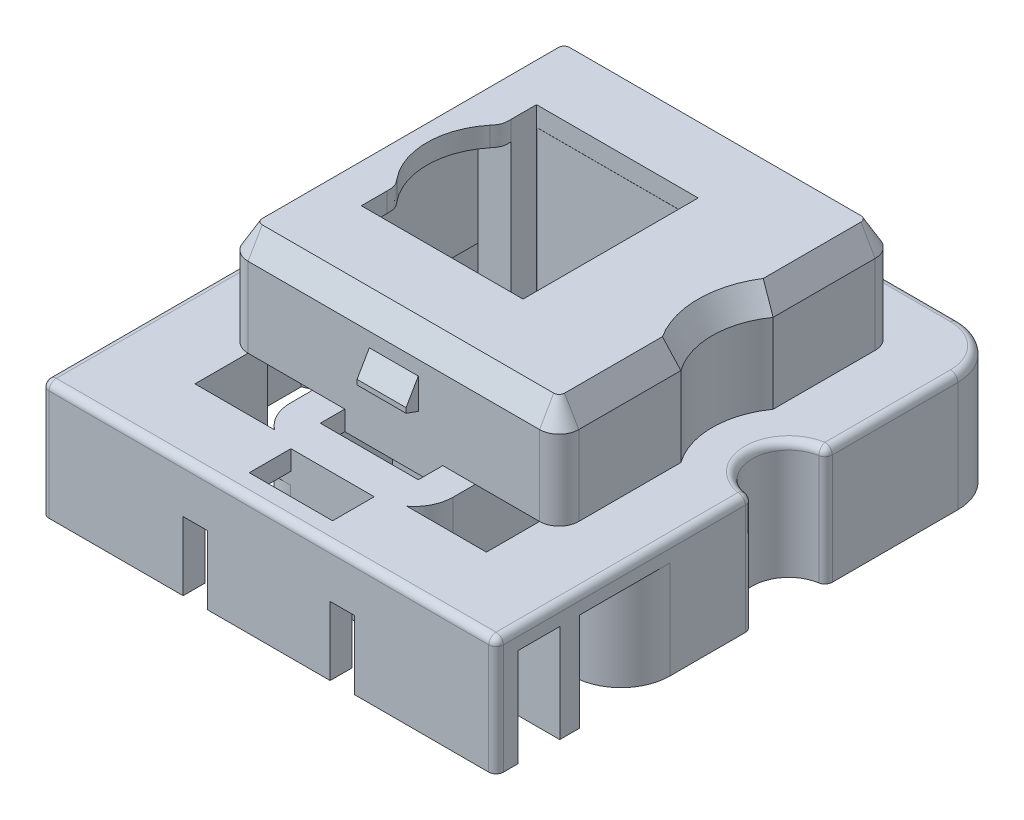
SolidWorks part; units mm, degrees
ref_plane "Front Plane" through (0, 0, 0) normal (0, 0, 1) x (1, 0, 0)
ref_plane "Top Plane" through (0, 0, 0) normal (0, 1, 0) x (1, 0, 0)
ref_plane "Right Plane" through (0, 0, 0) normal (1, 0, 0) x (0, 0, -1)
ref_plane "Floor" through (0, -4, 0) normal (0, -1, 0) x (-1, 0, 0)
sketch "Sketch1" plane through (0, 0, 0) normal (0, 1, 0) x (1, 0, 0)
  line L0 (9.275, -1.5) -> (9.275, -11.95)
  line L1 (-9.275, 8.9) -> (9.275, 8.9)
  line L2 (-9.275, 8.9) -> (-9.275, 1.5)
  line L3 (-9.275, -11.95) -> (9.275, -11.95)
  line L4 (9.275, 8.9) -> (9.275, 1.5)
  line L5 (-9.275, 8.9) -> (9.275, -11.95) construction
  line L6 (-9.275, -11.95) -> (9.275, 8.9) construction
  line L7 (-9.275, -1.5) -> (-9.275, -11.95)
  arc A0 (9.275, 1.5) -> (9.275, -1.5) centre (9.275, 0) ccw
  arc A1 (-9.275, -1.5) -> (-9.275, 1.5) centre (-9.275, 0) ccw
  point P0 (0, -1.525)
  dimension "D4" = 3
  dimension "D5" = 3
  dimension "D1" = 18.55
  dimension "D2" = 20.85
  dimension "D3" = 8.9
extrude "Boss-Extrude1" add sketch "Sketch1" along normal blind 0.8
sketch "Sketch2" plane through (0, 0.8, 0) normal (0, 1, 0) x (1, 0, 0)
  line L0 (6.75, -1.8815) -> (6.75, -6.85)
  line L1 (-6.75, 6.85) -> (6.75, 6.85)
  line L2 (-6.75, 6.85) -> (-6.75, -6.85)
  line L3 (-6.75, -6.85) -> (6.75, -6.85)
  line L4 (6.75, 6.85) -> (6.75, 1.8815)
  line L5 (-6.75, 6.85) -> (6.75, -6.85) construction
  line L6 (-6.75, -6.85) -> (6.75, 6.85) construction
  arc A0 (6.75, 1.8815) -> (6.75, -1.8815) centre (9.4, 0) ccw
  point P0 (0, 0)
  dimension "D3" = 6.5
  dimension "D1" = 13.5
  dimension "D2" = 13.7
  dimension "D4" = 9.4
extrude "Boss-Extrude2" add sketch "Sketch2" along normal blind 4.25
sketch "Sketch15" plane through (0, 0, 0) normal (0, -1, 0) x (1, 0, 0)
  line L0 (5.95, -2.1213) -> (5.95, -6.05)
  line L1 (5.95, 6.05) -> (-5.95, 6.05)
  line L2 (5.95, 6.05) -> (5.95, 2.1213)
  line L3 (5.95, -6.05) -> (-5.95, -6.05)
  line L4 (-5.95, 6.05) -> (-5.95, -6.05)
  line L5 (5.95, 6.05) -> (-5.95, -6.05) construction
  line L6 (5.95, -6.05) -> (-5.95, 6.05) construction
  arc A0 (5.95, 2.1213) -> (5.95, -2.1213) centre (9.4, 0) ccw
  point P0 (0, 0)
  dimension "D3" = 8.1
  dimension "D1" = 11.9
  dimension "D2" = 12.1
  dimension "D4" = 9.4
extrude "Cut-Extrude3" cut sketch "Sketch15" against normal blind 4.25
ref_plane "Plane2" through (0, 2.3, 0) normal (0, 1, 0) x (1, 0, 0)
sketch "Sketch6" plane through (0, 0, 6.85) normal (0, 0, 1) x (1, 0, 0)
  line L0 (-6.75, 0.8) -> (6.75, 0.8) construction
  line L1 (-1, 2.6) -> (1, 2.6)
  line L2 (-1, 2.6) -> (-1, 2.4)
  line L3 (-1, 2.4) -> (1, 2.4)
  line L4 (1, 2.6) -> (1, 2.4)
  line L5 (-1, 2.6) -> (1, 2.4) construction
  line L6 (-1, 2.4) -> (1, 2.6) construction
  point P0 (0, 2.5)
  dimension "D1" = 1.6
  dimension "D2" = 0.2
  dimension "D3" = 2
extrude "Boss-Extrude4" add sketch "Sketch6" along normal blind 0.5
draft "Draft1" type of draft neutral plane draft angle 60 faces to draft 1 face at (0, 2.6, 7.1) neutral plane through (0, 0, 7.35) neutral plane normal (0, 0, 1) parameters "D1"=60
draft "Draft4" type of draft neutral plane draft angle 20 faces to draft 1 face at (0, 2.4, 7.1) neutral plane through (0, 0, 7.35) neutral plane normal (0, 0, 1) parameters "D1"=20
sketch "Sketch7" plane through (0, 0.8, 0) normal (0, 1, 0) x (1, 0, 0)
  line L0 (-6.75, -6.85) -> (6.75, -6.85) construction
  line L1 (-2, -6.85) -> (2, -6.85)
  line L2 (-2, -6.85) -> (-2, -7.85)
  line L3 (-2, -7.85) -> (2, -7.85)
  line L4 (2, -6.85) -> (2, -7.85)
  line L5 (-2, -6.85) -> (2, -7.85) construction
  line L6 (-2, -7.85) -> (2, -6.85) construction
  point P0 (0, -7.35)
  dimension "D1" = 1
  dimension "D2" = 4
extrude "Cut-Extrude1" cut sketch "Sketch7" against normal through all
mirror "Mirror1" about plane through (0, 0, 0) normal (0, 0, 1) of "Draft4", "Draft1", "Boss-Extrude4", "Cut-Extrude1"
sketch "Sketch8" plane through (0, 0, 0) normal (0, 1, 0) x (1, 0, 0)
  line L1 (9.275, -11.05) -> (-9.275, -11.05)
  line L2 (9.275, -11.05) -> (9.275, -11.95)
  line L3 (9.275, -11.95) -> (-9.275, -11.95)
  line L4 (-9.275, -11.05) -> (-9.275, -11.95)
  line L5 (9.275, -11.05) -> (-9.275, -11.95) construction
  line L6 (9.275, -11.95) -> (-9.275, -11.05) construction
  line L8 (-9.275, -11.95) -> (9.275, -11.95) construction
  point P0 (0, -11.5)
  dimension "D1" = 0.9
extrude "Boss-Extrude5" add sketch "Sketch8" against normal up to surface (4 mm away) up to plane "Floor"
sketch "Sketch9" plane through (0, -4, 0) normal (0, -1, 0) x (-1, 0, 0)
  line L0 (9.275, -11.95) -> (-9.275, -11.95) construction
  line L1 (-9.275, -11.05) -> (9.275, -11.05) construction
  line L7 (-2.5, -11.95) -> (-3.5, -11.95)
  line L8 (-2.5, -11.95) -> (-2.5, -11.05)
  line L9 (-2.5, -11.05) -> (-3.5, -11.05)
  line L10 (-3.5, -11.95) -> (-3.5, -11.05)
  line L11 (-2.5, -11.95) -> (-3.5, -11.05) construction
  line L12 (-2.5, -11.05) -> (-3.5, -11.95) construction
  point P5 (-3, -11.5)
  dimension "D1" = 1
  dimension "D2" = 2.5
extrude "Cut-Extrude2" cut sketch "Sketch9" against normal blind 2.8
mirror "Mirror2" about plane through (0, 0, 0) normal (1, 0, 0) of "Cut-Extrude2"
sketch "Sketch11" plane through (0, 0, 0) normal (0, -1, 0) x (1, 0, 0)
  line L0 (9.275, 11.05) -> (9.275, 1.5) construction
  line L1 (5.95, 9.35) -> (9.275, 9.35)
  line L2 (5.95, 9.35) -> (5.95, 6.05)
  line L3 (9.275, 8.55) -> (6.75, 8.55)
  line L4 (9.275, 9.35) -> (9.275, 8.55)
  line L5 (9.275, 11.05) -> (-9.275, 11.05) construction
  line L6 (6.75, 8.55) -> (6.75, 6.85)
  line L7 (6.75, 6.85) -> (7.275, 6.85)
  line L8 (9.275, 4.85) -> (9.275, 1.5)
  line L9 (5.95, 6.05) -> (7.275, 6.05)
  line L10 (8.475, 4.85) -> (8.475, 2.1564)
  line L11 (9.275, -1.5) -> (9.275, -8.9)
  line L12 (9.275, -1.5) -> (9.275, -8.9) construction
  line L13 (8.475, -8.9) -> (8.475, -2.1564)
  line L14 (9.275, -8.9) -> (-9.275, -8.9) construction
  line L15 (8.475, -8.9) -> (9.275, -8.9)
  line L16 (5.95, 2.1213) -> (5.95, 6.05) construction
  line L17 (5.95, 6.05) -> (-5.95, 6.05) construction
  arc A0 (9.275, 1.5) -> (9.275, -1.5) centre (9.275, 0) ccw
  arc A1 (8.475, 2.1564) -> (8.475, -2.1564) centre (9.275, 0) ccw
  arc A2 (7.275, 6.05) -> (8.475, 4.85) centre (7.275, 4.85) cw
  arc A3 (7.275, 6.85) -> (9.275, 4.85) centre (7.275, 4.85) cw
  point P24 (9.275, 6.85)
  dimension "D4" = 3
  dimension "D5" = 4.6
  dimension "D10" = 1.2
  dimension "D11" = 2
  dimension "D1" = 1.7
  dimension "D2" = 0.8
  dimension "D6" = 0.8
  dimension "D7" = 0.8
  dimension "D8" = 0.8
  dimension "D12" = 0.8
extrude "Boss-Extrude6" add sketch "Sketch11" along normal up to surface (4 mm away) up to plane "Floor"
sketch "Sketch12" plane through (0, 0, 0) normal (0, -1, 0) x (1, 0, 0)
  line L1 (5.95, 11.05) -> (6.75, 11.05)
  line L2 (5.95, 11.05) -> (5.95, 9.35)
  line L3 (5.95, 9.35) -> (6.75, 9.35)
  line L4 (6.75, 11.05) -> (6.75, 9.35)
  line L5 (9.275, 11.05) -> (-9.275, 11.05) construction
  line L6 (9.275, 9.35) -> (5.95, 9.35) construction
  line L7 (5.95, 9.35) -> (5.95, 6.05) construction
  line L8 (6.75, 6.85) -> (6.75, 8.55) construction
extrude "Boss-Extrude7" add sketch "Sketch12" along normal blind 1.5
mirror "Mirror3" about plane through (0, 0, 0) normal (1, 0, 0) of "Boss-Extrude7", "Boss-Extrude6"
sketch "Sketch19" plane through (0, 0, 0) normal (0, -1, 0) x (1, 0, 0)
  line L0 (8.475, -8.9) -> (-8.475, -8.9) construction
  line L1 (-4.55, -3.57) -> (4.55, -3.57)
  line L2 (-4.55, -3.57) -> (-4.55, -8.9)
  line L3 (-4.55, -8.9) -> (4.55, -8.9)
  line L4 (4.55, -3.57) -> (4.55, -8.9)
  line L5 (-4.55, -3.57) -> (4.55, -8.9) construction
  line L6 (-4.55, -8.9) -> (4.55, -3.57) construction
  line L8 (-3.75, -8.1) -> (3.75, -8.1)
  line L9 (-3.75, -8.1) -> (-3.75, -4.37)
  line L10 (-3.75, -4.37) -> (3.75, -4.37)
  line L11 (3.75, -8.1) -> (3.75, -4.37)
  line L12 (-3.75, -8.1) -> (3.75, -4.37) construction
  line L13 (-3.75, -4.37) -> (3.75, -8.1) construction
  point P0 (0, -6.235)
  point P7 (0, -8.9)
  point P9 (0, -6.235)
  dimension "D1" = 5.33
  dimension "D2" = 9.1
  dimension "D3" = 0.8
  dimension "D4" = 0.8
sketch "Sketch13" plane through (0, 0, 0) normal (0, -1, 0) x (1, 0, 0)
  line L0 (8.475, -8.9) -> (-8.475, -8.9) construction
  line L1 (8.475, -8.1) -> (-8.475, -8.1)
  line L2 (8.475, -8.1) -> (8.475, -8.9)
  line L3 (8.475, -8.9) -> (-8.475, -8.9)
  line L4 (-8.475, -8.1) -> (-8.475, -8.9)
  line L5 (8.475, -8.1) -> (-8.475, -8.9) construction
  line L6 (8.475, -8.9) -> (-8.475, -8.1) construction
  point P0 (0, -8.5)
  point P7 (0, -8.9)
  dimension "D1" = 0.8
extrude "Boss-Extrude8" add sketch "Sketch13" along normal up to surface (4 mm away) up to plane "Floor"
fillet "Fillet1" radius 1.2 2 edges at (8.475, -2, -8.1) (-8.475, -2, -8.1)
fillet "Fillet2" radius 2 2 edges at (9.275, -1.6, -8.9) (-9.275, -1.6, -8.9)
fillet "Fillet3" radius 0.3 16 edges at (9.275, 0.8, -4.2) (8.6892, 0.8, -8.3142) (0, 0.8, -8.9) (-8.6892, 0.8, -8.3142) (7.775, 0.8, 0) (-7.775, 0.8, 0) (-9.275, 0.8, 6.725) (0, 0.8, 11.95) (9.275, 0.8, 6.725) (-9.275, 0.8, -4.2) (-9.275, -1.6, -1.5) (-9.275, -1.6, 1.5) (9.275, -1.6, -1.5) (9.275, -1.6, 1.5) (-9.275, -1.6, 11.95) (9.275, -1.6, 11.95)
fillet "Fillet5" radius 0.8 4 edges at (-6.75, 2.925, -6.85) (6.75, 2.925, -6.85) (-6.75, 2.925, 6.85) (6.75, 2.925, 6.85)
chamfer "Chamfer1" distance 1 angle 30 10 edges at (6.5157, 5.05, -6.6157) (0, 5.05, -6.85) (-6.5157, 5.05, -6.6157) (-6.75, 5.05, 0) (-6.5157, 5.05, 6.6157) (6.75, 5.05, -3.9657) (0, 5.05, 6.85) (6.75, 5.05, 3.9657) (6.5157, 5.05, 6.6157) (6.15, 5.05, 0) first distance on face at (6.4328, 2.925, -6.5328) first distance on face at (0, 2.842, -6.85) first distance on face at (-6.4328, 2.925, -6.5328) first distance on face at (-6.75, 2.925, 0) first distance on face at (-6.4328, 2.925, 6.5328) first distance on face at (6.75, 2.925, -3.9657) first distance on face at (0, 1.6625, 6.85) first distance on face at (6.75, 2.925, 3.9657) first distance on face at (6.4328, 2.925, 6.5328) first distance on face at (6.45, 2.925, 0)
sketch "Sketch14" plane through (0, 0, 0) normal (0, -1, 0) x (1, 0, 0)
  line L0 (9.275, 9.35) -> (6.75, 9.35) construction
  line L1 (-1.725, 9.35) -> (1.725, 9.35)
  line L2 (-3.325, 7.75) -> (-3.325, 3.57)
  line L3 (-3.325, 3.57) -> (3.325, 3.57)
  line L4 (3.325, 7.75) -> (3.325, 3.57)
  line L5 (-3.325, 9.35) -> (3.325, 3.57) construction
  line L6 (-3.325, 3.57) -> (3.325, 9.35) construction
  line L8 (-1.725, 8.55) -> (1.725, 8.55)
  line L9 (-2.525, 7.75) -> (-2.525, 4.37)
  line L10 (-2.525, 4.37) -> (2.525, 4.37)
  line L11 (2.525, 7.75) -> (2.525, 4.37)
  line L12 (-2.525, 8.55) -> (2.525, 4.37) construction
  line L13 (-2.525, 4.37) -> (2.525, 8.55) construction
  arc A0 (-1.725, 9.35) -> (-3.325, 7.75) centre (-1.725, 7.75) ccw
  arc A1 (1.725, 9.35) -> (3.325, 7.75) centre (1.725, 7.75) cw
  arc A2 (-1.725, 8.55) -> (-2.525, 7.75) centre (-1.725, 7.75) ccw
  arc A3 (1.725, 8.55) -> (2.525, 7.75) centre (1.725, 7.75) cw
  point P0 (0, 6.46)
  point P10 (0, 6.46)
  dimension "D5" = 1.6
  dimension "D6" = 0.8
  dimension "D1" = 6.65
  dimension "D2" = 5.78
  dimension "D3" = 0.8
  dimension "D4" = 0.8
extrude "Boss-Extrude9" add sketch "Sketch14" along normal up to surface (4 mm away) up to plane "Floor"
sketch "Sketch16" plane through (0, 0, 0) normal (0, -1, 0) x (1, 0, 0)
  line L8 (-3.325, 6.05) -> (-3.325, 3.57)
  line L9 (-2.525, 6.05) -> (-3.325, 6.05)
  line L10 (-2.525, 4.37) -> (-2.525, 6.05)
  line L11 (2.525, 4.37) -> (-2.525, 4.37)
  line L12 (2.525, 6.05) -> (2.525, 4.37)
  line L13 (3.325, 6.05) -> (2.525, 6.05)
  line L14 (3.325, 3.57) -> (3.325, 6.05)
  line L15 (-3.325, 3.57) -> (3.325, 3.57)
  line L16 (-3.325, 6.05) -> (-3.325, 3.57)
  line L17 (-2.525, 6.05) -> (-3.325, 6.05)
  line L18 (-2.525, 4.37) -> (-2.525, 6.05)
  line L19 (2.525, 4.37) -> (-2.525, 4.37)
  line L20 (2.525, 6.05) -> (2.525, 4.37)
  line L21 (3.325, 6.05) -> (2.525, 6.05)
  line L22 (3.325, 3.57) -> (3.325, 6.05)
  line L23 (-3.325, 3.57) -> (3.325, 3.57)
  dimension "D1" = 0
extrude "Boss-Extrude10" add sketch "Sketch16" against normal up to surface (4.25 mm away) up to face at (1.8833, 4.25, 0)
sketch "Sketch17" plane through (0, 0, 0) normal (0, -1, 0) x (1, 0, 0)
  line L0 (5.95, 11.05) -> (-5.95, 11.05) construction
  line L1 (-1.7, 11.05) -> (1.7, 11.05)
  line L2 (-1.7, 11.05) -> (-1.7, 9.35)
  line L3 (-1.7, 9.35) -> (1.7, 9.35)
  line L4 (1.7, 11.05) -> (1.7, 9.35)
  line L5 (-1.7, 11.05) -> (1.7, 9.35) construction
  line L6 (-1.7, 9.35) -> (1.7, 11.05) construction
  line L7 (1.725, 9.35) -> (-1.725, 9.35) construction
  point P0 (0, 10.2)
  dimension "D1" = 3.4
extrude "Cut-Extrude4" cut sketch "Sketch17" against normal through all
sketch "Sketch18" plane through (0, 0, 11.05) normal (0, 0, -1) x (-1, 0, 0)
  line L1 (1.4, -3.1) -> (-1.4, -3.1)
  line L2 (1.4, -3.1) -> (1.4, -3.3)
  line L3 (1.4, -3.3) -> (-1.4, -3.3)
  line L4 (-1.4, -3.1) -> (-1.4, -3.3)
  line L5 (1.4, -3.1) -> (-1.4, -3.3) construction
  line L6 (1.4, -3.3) -> (-1.4, -3.1) construction
  line L7 (-6.75, -1.5) -> (-5.95, -1.5) construction
  point P0 (0, -3.2)
  dimension "D1" = 1.6
  dimension "D2" = 0.2
  dimension "D3" = 2.8
extrude "Boss-Extrude11" add sketch "Sketch18" along normal blind 0.25
draft "Draft2" type of draft neutral plane draft angle 60 faces to draft 1 face at (0, -3.3, 10.925) neutral plane through (0, 0, 10.8) neutral plane normal (0, 0, -1) parameters "D1"=60
draft "Draft3" type of draft neutral plane draft angle 20 faces to draft 1 face at (0, -3.1, 10.925) neutral plane through (0, 0, 10.8) neutral plane normal (0, 0, -1) parameters "D1"=20
ref_plane "Plane4" through (0, 0, 10.2) normal (0, 0, -1) x (-1, 0, 0)
mirror "Mirror4" about plane through (0, 0, 10.2) normal (0, 0, -1) of "Draft3", "Draft2", "Boss-Extrude11"
extrude "Boss-Extrude12" add sketch "Sketch19" along normal up to surface (4 mm away) up to plane "Floor"
sketch "Sketch20" plane through (0, 0, 0) normal (0, -1, 0) x (1, 0, 0)
  line L8 (4.55, -6.05) -> (4.55, -3.57)
  line L9 (3.75, -6.05) -> (4.55, -6.05)
  line L10 (3.75, -4.37) -> (3.75, -6.05)
  line L11 (-3.75, -4.37) -> (3.75, -4.37)
  line L12 (-3.75, -6.05) -> (-3.75, -4.37)
  line L13 (-4.55, -6.05) -> (-3.75, -6.05)
  line L14 (-4.55, -3.57) -> (-4.55, -6.05)
  line L15 (4.55, -3.57) -> (-4.55, -3.57)
  line L16 (4.55, -6.05) -> (4.55, -3.57)
  line L17 (3.75, -6.05) -> (4.55, -6.05)
  line L18 (3.75, -4.37) -> (3.75, -6.05)
  line L19 (-3.75, -4.37) -> (3.75, -4.37)
  line L20 (-3.75, -6.05) -> (-3.75, -4.37)
  line L21 (-4.55, -6.05) -> (-3.75, -6.05)
  line L22 (-4.55, -3.57) -> (-4.55, -6.05)
  line L23 (4.55, -3.57) -> (-4.55, -3.57)
  dimension "D1" = 0
extrude "Boss-Extrude13" add sketch "Sketch20" against normal up to surface (4.25 mm away) up to face at (1.13, 4.25, 1.924)
sketch "Sketch21" plane through (0, 0, 0) normal (0, -1, 0) x (1, 0, 0)
  line L0 (2.7, 11.05) -> (2.7, 9.0186) construction
  line L1 (5.95, 11.05) -> (1.7, 11.05) construction
  line L2 (1.7, 9.35) -> (1.7, 11.05) construction
  line L3 (2.7, 9.0186) -> (5.95, 9.0186)
  line L9 (5.95, 11.05) -> (1.7, 11.05)
  line L10 (1.7, 11.05) -> (1.7, 9.35)
  line L11 (1.7, 9.35) -> (1.725, 9.35)
  line L12 (3.325, 7.75) -> (3.325, 6.05)
  line L13 (3.325, 6.05) -> (5.95, 6.05)
  line L14 (5.95, 6.05) -> (5.95, 11.05)
  line L18 (3.325, 7.75) -> (3.325, 6.05)
  line L19 (3.325, 6.05) -> (5.95, 6.05)
  line L20 (5.95, 6.05) -> (5.95, 9.0186)
  arc A0 (3.325, 7.75) -> (1.725, 9.35) centre (1.725, 7.75) ccw construction
  arc A2 (3.325, 7.75) -> (1.725, 9.35) centre (1.725, 7.75) ccw
  arc A3 (3.325, 7.75) -> (2.7, 9.0186) centre (1.725, 7.75) ccw
  dimension "D1" = 1
  dimension "D2" = 0
extrude "Cut-Extrude5" cut sketch "Sketch21" against normal up to surface (0.8 mm away) up to face at (0, 0.8, 10.2)
sketch "Sketch22" plane through (0, 0, 0) normal (0, -1, 0) x (1, 0, 0)
  line L0 (1.725, 9.35) -> (5.95, 9.35)
  line L5 (2.7, 9.0186) -> (5.95, 9.0186)
  line L6 (5.95, 9.0186) -> (5.95, 11.05)
  line L7 (5.95, 11.05) -> (1.7, 11.05)
  line L8 (1.7, 11.05) -> (1.7, 9.35)
  line L9 (1.7, 9.35) -> (1.725, 9.35)
  line L10 (2.7, 9.0186) -> (5.95, 9.0186)
  line L11 (5.95, 9.0186) -> (5.95, 9.35)
  arc A1 (2.7, 9.0186) -> (1.725, 9.35) centre (1.725, 7.75) ccw
  arc A2 (2.7, 9.0186) -> (1.725, 9.35) centre (1.725, 7.75) ccw
  dimension "D1" = 0
extrude "Boss-Extrude14" add sketch "Sketch22" along normal blind 0.5
mirror "Mirror5" about plane through (0, 0, 0) normal (1, 0, 0) of "Boss-Extrude14", "Cut-Extrude5"
chamfer "Chamfer2" distance 0.5 angle 30 2 edges at (4.6375, 0.8, 6.05) (-4.6375, 0.8, 6.05) first distance on face at (4.6375, 2.525, 6.05) first distance on face at (-4.6375, 0.8, 6.45)
sketch "Sketch23" plane through (0, 5.05, 0) normal (0, 1, 0) x (1, 0, 0)
  line L0 (0, -1000) -> (0, 49000) construction
  line L1 (1.9, -1001.0023) -> (1.9, 48998.9977) construction
  line L2 (-2.5, -1002.0635) -> (-2.5, 48997.9365) construction
  line L3 (-4.5, -1002.4785) -> (-4.5, 48997.5215) construction
  line L4 (-1000, 0) -> (49000, 0) construction
  line L6 (-4.6, 3.575) -> (2, 3.575)
  line L7 (-4.6, 3.575) -> (-4.6, -3.575)
  line L8 (-4.6, -3.575) -> (2, -3.575)
  line L9 (2, 3.575) -> (2, -3.575)
  line L10 (-4.6, 3.575) -> (2, -3.575) construction
  line L11 (-4.6, -3.575) -> (2, 3.575) construction
  point P10 (-1.3, 0)
  point P16 (0, 0)
  dimension "D1" = 1.9
  dimension "D2" = 2.5
  dimension "D3" = 2
  dimension "D4" = 7.15
  dimension "D5" = 0.1
  dimension "D6" = 0.1
extrude "Cut-Extrude6" cut sketch "Sketch23" against normal up to surface (0.8 mm away) up to face at (0.8071, 4.25, 0)
sketch "Sketch5" plane through (0, 5.05, 0) normal (0, 1, 0) x (1, 0, 0)
  circle A0 centre (-2.5, 0) radius 2.75 construction
  circle A1 centre (9.4, 0) radius 2.75 construction
  circle A2 centre (-2.5, 0) radius 3
  point P0 (-2.5, 0)
  dimension "D2" = 5.5
  dimension "D4" = 0.25
  dimension "D1" = 2.5
  dimension "D3" = 11.9
extrude "Cut-Extrude7" cut sketch "Sketch5" against normal up to surface (0.8 mm away) up to face at (4.295, 4.25, 0)
fillet "Fillet6" radius 1 2 edges at (-4.6, 4.65, 2.1424) (-4.6, 4.65, -2.1424) conic rho 0.65
sketch "Sketch24" plane through (0, 4.25, 0) normal (0, -1, 0) x (1, 0, 0)
  line L0 (2, 3.57) -> (2, -3.57) construction
  line L1 (2, 1.07) -> (3.325, 1.07)
  line L2 (2, 1.07) -> (2, 3.57)
  line L3 (2, 3.57) -> (3.325, 3.57)
  line L4 (3.325, 1.07) -> (3.325, 3.57)
  dimension "D1" = 2.5
extrude "Boss-Extrude15" add sketch "Sketch24" along normal up to surface (8.25 mm away) up to plane "Floor"
sketch "Sketch25" plane through (0, 4.25, 0) normal (0, -1, 0) x (1, 0, 0)
  line L0 (-4.6, -2.5278) -> (-5.95, -2.5278)
  line L9 (-4.6, 2.5278) -> (-4.6, 3.575)
  line L10 (-4.6, 3.575) -> (-3.325, 3.575)
  line L11 (-3.325, 3.575) -> (-3.325, 6.05)
  line L12 (-3.325, 6.05) -> (-5.95, 6.05)
  line L13 (-5.95, 6.05) -> (-5.95, -6.05)
  line L14 (-5.95, -6.05) -> (-4.55, -6.05)
  line L15 (-4.55, -6.05) -> (-4.55, -3.575)
  line L16 (-4.55, -3.575) -> (-4.6, -3.575)
  line L17 (-4.6, -3.575) -> (-4.6, -2.5278)
  line L22 (-5.95, -2.5278) -> (-5.95, -6.05)
  line L23 (-5.95, -6.05) -> (-4.55, -6.05)
  line L24 (-4.55, -6.05) -> (-4.55, -3.575)
  line L25 (-4.55, -3.575) -> (-4.6, -3.575)
  line L26 (-4.6, -3.575) -> (-4.6, -2.5278)
  arc A1 (-4.825, 1.8959) -> (-4.825, -1.8959) centre (-2.5, 0) ccw
  spline S2 degree 2 poles (-763.7121, -649.3259) (-11.6988, -8.1487) (-4.7202, 2.0337) (-4.6654, 2.1138) (-4.6394, 2.1858) (-4.6146, 2.2546) (-4.6059, 2.3549) (-3.6561, 13.3008) (-155.8379, 991.0247) knots -43.259373 -43.259373 -43.259373 0.25 0.25 0.5 0.5 0.75 0.75 41.055514 41.055514 41.055514 only from (-4.825, 1.8959) to (-4.6, 2.5278)
  spline S3 degree 2 poles (-181.1906, -986.812) (-3.5795, -14.6564) (-4.6059, -2.3548) (-4.614, -2.2581) (-4.6394, -2.1859) (-4.6636, -2.1169) (-4.7202, -2.0337) (-10.9015, 7.0497) (-746.7261, 668.6126) knots -43.259373 -43.259373 -43.259373 0.25 0.25 0.5 0.5 0.75 0.75 41.055514 41.055514 41.055514 only from (-4.6, -2.5278) to (-4.825, -1.8959)
  dimension "D1" = 0
extrude "Boss-Extrude16" add sketch "Sketch25" along normal up to surface (8.25 mm away) up to plane "Floor"
